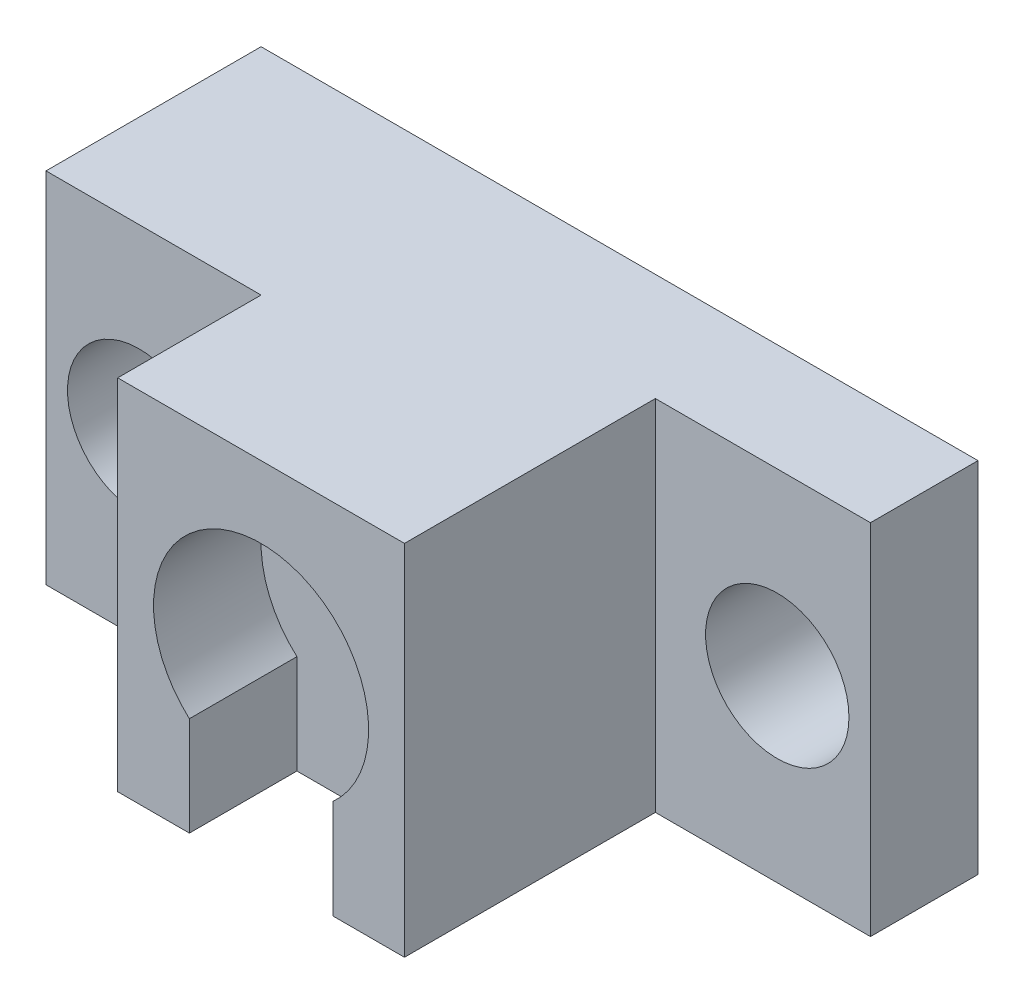
SolidWorks part; units mm, degrees
ref_plane "Front Plane" through (0, 0, 0) normal (0, 0, 1) x (1, 0, 0)
ref_plane "Top Plane" through (0, 0, 0) normal (0, 1, 0) x (1, 0, 0)
ref_plane "Right Plane" through (0, 0, 0) normal (1, 0, 0) x (0, 0, -1)
sketch "Sketch1" plane through (0, 0, 0) normal (0, 0, 1) x (1, 0, 0)
  line L1 (-50, 59.3607) -> (50, 59.3607)
  line L2 (-50, 59.3607) -> (-50, 9.3607)
  line L3 (-50, 9.3607) -> (50, 9.3607)
  line L4 (50, 59.3607) -> (50, 9.3607)
  line L5 (-50, 59.3607) -> (-20, 59.3607)
  line L6 (-50, 59.3607) -> (-50, 9.3607)
  line L7 (-50, 9.3607) -> (-20, 9.3607)
  line L8 (-20, 59.3607) -> (-20, 9.3607)
  line L9 (-20, 9.3607) -> (20, 9.3607)
  line L10 (-20, 9.3607) -> (-20, 59.3607)
  line L11 (-20, 59.3607) -> (20, 59.3607)
  line L12 (20, 9.3607) -> (20, 59.3607)
  dimension "D1" = 50
  dimension "D2" = 100
  dimension "D3" = 40
  dimension "D4" = 30
extrude "Boss-Extrude1" add sketch "Sketch1" along normal blind 50 contours L3 L12 L1 L8 region at (0, 34.3607, 0)
extrude "Boss-Extrude2" add sketch "Sketch1<3>" along normal blind 30 contours L8 L1 L2 L3 region at (-35, 34.3607, 0)
sketch "Sketch1<3>" plane through (0, 0, 0) normal (0, 0, 1) x (1, 0, 0) same geometry as "Sketch1"
extrude "Boss-Extrude3" add sketch "Sketch1<4>" along normal blind 15 contours L12 L3 L4 L1 region at (35, 34.3607, 0)
sketch "Sketch1<4>" plane through (0, 0, 0) normal (0, 0, 1) x (1, 0, 0) same geometry as "Sketch1"
sketch "Sketch2" plane through (0, 0, 50) normal (0, 0, 1) x (1, 0, 0)
  line L0 (-20, 59.3607) -> (-20, 9.3607) construction
  line L2 (-20, 9.3607) -> (20, 9.3607) construction
  line L3 (-10, 23.1804) -> (-10, 9.3607)
  line L4 (10, 23.1804) -> (10, 9.3607)
  line L5 (-10, 9.3607) -> (10, 9.3607)
  arc A0 (10, 23.1804) -> (-10, 23.1804) centre (0, 34.3607) ccw
  point P10 (0, 9.3607)
  dimension "D1" = 30
  dimension "D2" = 20
  dimension "D3" = 25
  dimension "D4" = 10
extrude "Cut-Extrude1" cut sketch "Sketch2" against normal blind 15 contours A0 L3 L5 L4
sketch "Sketch3" plane through (0, 0, 30) normal (0, 0, 1) x (1, 0, 0)
  line L0 (-50, 59.3607) -> (-20, 59.3607) construction
  line L1 (-50, 59.3607) -> (-50, 9.3607) construction
  line L2 (20, 59.3607) -> (50, 59.3607) construction
  line L3 (50, 59.3607) -> (50, 9.3607) construction
  circle A0 centre (-37, 34.3607) radius 10
  circle A1 centre (37, 34.3607) radius 10
  point P8 (36.1308, 34.3607)
  dimension "D1" = 25
  dimension "D3" = 20
  dimension "D2" = 13
  dimension "D4" = 25
  dimension "D5" = 13
extrude "Cut-Extrude2" cut sketch "Sketch3" against normal through all contours A0 | A1
